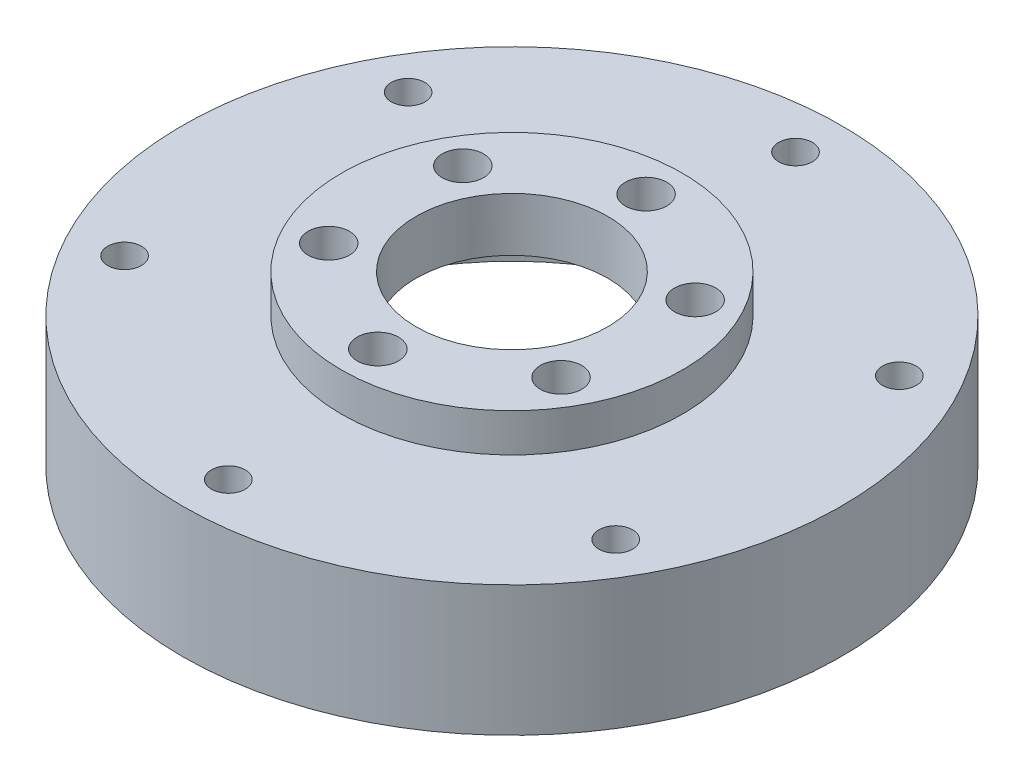
SolidWorks part; units mm, degrees
ref_plane "Front Plane" through (0, 0, 0) normal (0, 0, 1) x (1, 0, 0)
ref_plane "Top Plane" through (0, 0, 0) normal (0, 1, 0) x (1, 0, 0)
ref_plane "Right Plane" through (0, 0, 0) normal (1, 0, 0) x (0, 0, -1)
sketch "스케치22" plane through (0, 0, 0) normal (0, 1, 0) x (1, 0, 0)
  circle A0 centre (0, 0) radius 43
  circle A1 centre (0, 0) radius 22.5
  dimension "D1" = 86
  dimension "D2" = 45
extrude "보스-돌출5" add sketch "스케치22" along normal blind 17 contours A0
sketch "스케치24" plane through (0, 17, 0) normal (0, 1, 0) x (1, 0, 0)
  circle A0 centre (0, 0) radius 22.5 construction
  circle A2 centre (0, 0) radius 22.244
  dimension "D1" = 45
extrude "보스-돌출6" add sketch "스케치24" along normal blind 5
sketch "스케치25" plane through (0, 0, 0) normal (0, -1, 0) x (1, 0, 0)
  circle A3 centre (0, 0) radius 32.5 construction
  circle A4 centre (0, 0) radius 32.76
  dimension "D1" = 65
extrude "컷-돌출9" cut sketch "스케치25" against normal blind 15
sketch "스케치26" plane through (0, 22, 0) normal (0, 1, 0) x (1, 0, 0)
  circle A0 centre (0, 0) radius 12.5
  circle A1 centre (0, 0) radius 12.7
  dimension "D1" = 25
extrude "컷-돌출10" cut sketch "스케치26" against normal blind 10 contours A0
sketch "스케치27" plane through (0, 22, 0) normal (0, 1, 0) x (1, 0, 0)
  arc A0 (-2.692, 17.2917) -> (2.692, 17.2917) centre (0, 0) ccw
  circle A1 centre (0, 17.5) radius 2.7
  point P3 (0, 17.5)
  dimension "D1" = 35
  dimension "D2" = 5.4
sketch "스케치29" plane through (0, 17, 0) normal (0, 1, 0) x (1, 0, 0)
  line L0 (0, 0) -> (0, 48.7999) construction
  circle A0 centre (0, 0) radius 37
  circle A1 centre (0, 37) radius 2.2
  point P3 (0, 37)
  dimension "D1" = 74
  dimension "D2" = 4.4
extrude "컷-돌출11" cut sketch "스케치27" against normal blind 6.1 contours A1
pattern_circular "원형 패턴6" count 6 over 360 about axis through (0, 22, 0) along (0, 1, 0) of "컷-돌출11"
extrude "컷-돌출12" cut sketch "스케치29" against normal through all contours A1
pattern_circular "원형 패턴7" count 6 over 360 about axis through (0, 22, 0) along (0, 1, 0) of "컷-돌출12"
equation "\"Diameter\"= 86"
equation "\"D1@스케치22\"=\"Diameter\""
equation "\"Bearing_Diameter\"= 45"
equation "\"D1@스케치24\"=\"Bearing_Diameter\""
equation "\"Bearing_Height\"= 5"
equation "\"D1@보스-돌출6\"=\"Bearing_Height\""
equation "\"Inner_diameter\"= \"Motor_Diameter\" + 2"
equation "\"Center_Gap\"= 25"
equation "\"D1@스케치26\"=\"Center_Gap\""
equation "\"Shoulder_Pin_Line\"= 17.5 * 2"
equation "\"D1@스케치27\"=\"Shoulder_Pin_Line\""
equation "\"Screw_Placement_Diameter\"= 74"
equation "\"D1@스케치29\"=\"Screw_Placement_Diameter\""
equation "\"D2@스케치22\"=\"Bearing_Diameter\""
equation "\"Top_Shell_Height\"= 17"
equation "\"D1@보스-돌출5\"=\"Top_Shell_Height\""
equation "\"D1@컷-돌출9\"=\"Top_Shell_Height\"-2"
equation "\"TOL\"= 0.2mm"
equation "\"Shoulder_Pin_Diameter\"=4.4"
equation "\"M3-Thread-Hole\"= 4.4"
equation "\"D2@스케치29\"=\"M3-Thread-Hole\""
equation "\"Motor_Diameter\"= 63"
equation "\"D1@스케치25\"=\"Inner_diameter\""
equation "\"M4 - Thread - Hole\"= 5.9"
